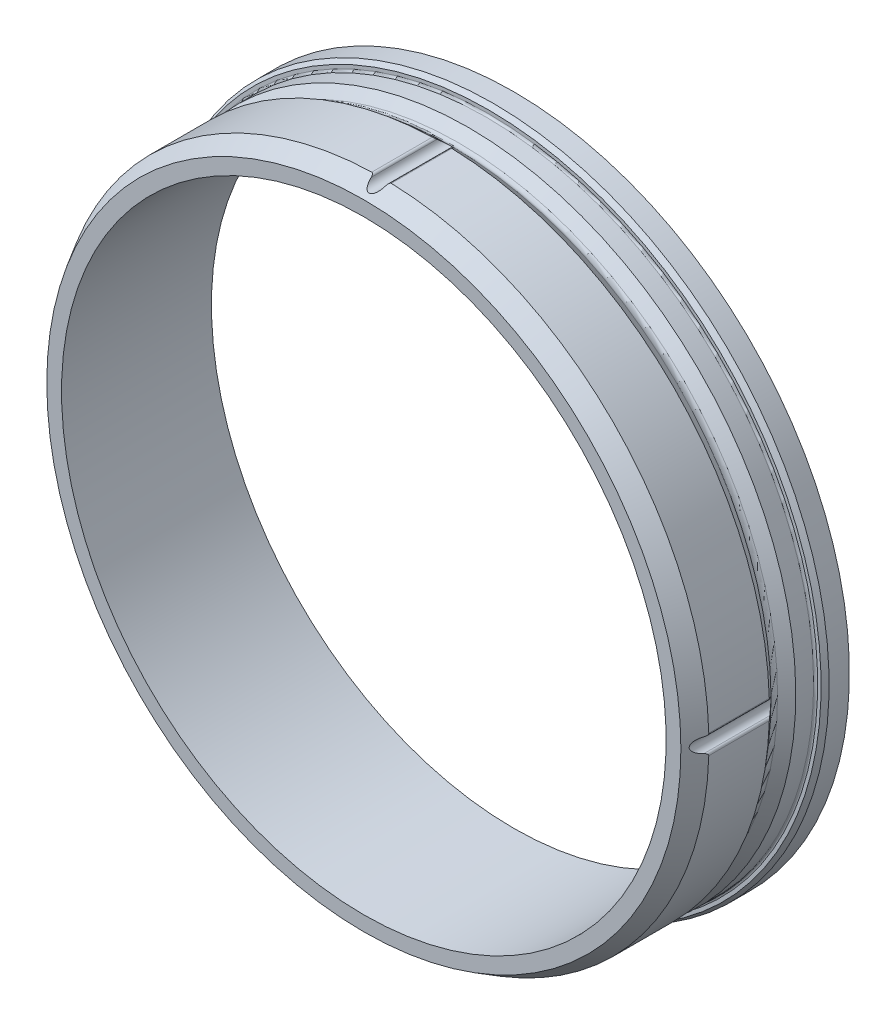
SolidWorks part; units mm, degrees
material "PB01 (C90710) Bronze"
ref_plane "Front Plane" through (0, 0, 0) normal (0, 0, 1) x (1, 0, 0)
ref_plane "Top Plane" through (0, 0, 0) normal (0, 1, 0) x (1, 0, 0)
ref_plane "Right Plane" through (0, 0, 0) normal (1, 0, 0) x (0, 0, -1)
sketch "Sketch1" plane through (0, 0, 0) normal (1, 0, 0) x (0, 0, -1)
  line L0 (0, 0) -> (-178.1962, 0) construction
  line L1 (0, 66.075) -> (-4, 66.075)
  line L2 (-4, 66.075) -> (-5, 65.4976)
  line L3 (-5, 65.4976) -> (-5, 64.825)
  line L4 (-14.0921, 64.425) -> (-26, 64.425)
  line L5 (-29.5, 62.4043) -> (-29.5, 59.5)
  line L6 (-29.5, 59.5) -> (0, 59.5)
  line L7 (0, 66.075) -> (0, 59.5)
  line L8 (-29.5, 62.4043) -> (-26, 64.425)
  line L9 (-14.0921, 64.425) -> (-12.1428, 62.7894)
  line L10 (-10.8572, 62.7894) -> (-8.9079, 64.425)
  line L11 (-11.5, 62.25) -> (-11.5, 70.7468) construction
  line L12 (-8.9079, 64.425) -> (-5.4, 64.425)
  arc A0 (-5, 64.825) -> (-5.4, 64.425) centre (-5.4, 64.825) cw
  arc A1 (-12.1428, 62.7894) -> (-10.8572, 62.7894) centre (-11.5, 63.5554) ccw
  dimension "D8" = 0.4
  dimension "D14" = 1
  dimension "D15" = 125.1108
  dimension "D1" = 119
  dimension "D2" = 132.15
  dimension "D3" = 128.85
  dimension "D4" = 1
  dimension "D5" = 30
  dimension "D6" = 5
  dimension "D7" = 29.5
  dimension "D9" = 3.5
  dimension "D10" = 30
  dimension "D11" = 11.5
  dimension "D12" = 100
  dimension "D13" = 124.5
revolve "Revolve1" add sketch "Sketch1" angle 360 about L0
sketch "Sketch2" plane through (0, 0, 29.5) normal (0, 0, 1) x (1, 0, 0)
  line L0 (0, 0) -> (0, 50.9619) construction
  line L1 (0, 0) -> (38.5637, 0) construction
  line L2 (-1.5, 71.6061) -> (1.5, 71.6061)
  line L3 (-1.5, 71.6061) -> (-1.5, 64.5)
  line L4 (-1.5, 63) -> (1.5, 63) construction
  line L5 (1.5, 71.6061) -> (1.5, 64.5)
  arc A0 (-1.5, 64.5) -> (1.5, 64.5) centre (0, 64.5) ccw
  dimension "D4" = 7.1061
  dimension "D1" = 63
  dimension "D2" = 3
  dimension "D3" = 8.6061
extrude "Cut-Extrude1" cut sketch "Sketch2" against normal up to surface (6.8311 mm away) up to face at (0, 64.425, 14.0921)
fillet "Fillet2" radius 0.5 2 edges at (1.4972, 64.4076, 20.046) (-1.4972, 64.4076, 20.046)
pattern_circular "CirPattern1" count 4 over 360 about axis through (0, 0, 0) along (0, 0, -1) of "Cut-Extrude1", "Fillet2"
sketch "Sketch3" plane through (0, 0, 0) normal (1, 0, 0) x (0, 0, -1)
  line L0 (0, 0) -> (-52.7276, 0) construction
  line L1 (-1, 68.3446) -> (-1, 60.045)
  line L2 (-1, 60.045) -> (-15.7584, 60.045)
  line L3 (0, -59.5) -> (0, 59.5) construction
  line L4 (-25.2416, 60.045) -> (-29.5, 60.045)
  line L5 (-17.2416, 60.045) -> (-23.7584, 60.045)
  line L6 (-29.5, 60.045) -> (-29.5, 54.0113)
  line L7 (-1, 68.3446) -> (3.25, 68.3446)
  line L8 (3.25, 68.3446) -> (3.25, 54.0113)
  line L9 (-29.5, 54.0113) -> (3.25, 54.0113)
  line L10 (-29.5, 59.5) -> (-29.5, -59.5) construction
  arc A0 (-15.7584, 60.045) -> (-17.2416, 60.045) centre (-16.5, 59.745) ccw
  arc A1 (-23.7584, 60.045) -> (-25.2416, 60.045) centre (-24.5, 59.745) ccw
  dimension "D1" = 0.5
  dimension "D2" = 1.6
  dimension "D5" = 15.5
  dimension "D6" = 23.5
  dimension "D3" = 1
  dimension "D4" = 120.09
  dimension "D7" = 108.0226
  dimension "D8" = 14.3333
  dimension "D9" = 4.25
revolve "Cut-Revolve1" [suppressed] cut sketch "Sketch3" angle 360 about L0
chamfer "Chamfer1" [suppressed] distance 0.25 angle 45
ref_axis "Axis1" through (0, 0, 30.925) along (0, 0, -1)
ref_plane "Plane1" through (0, 0, 0) normal (0.7071, -0.7071, 0) x (0, 0, -1)
